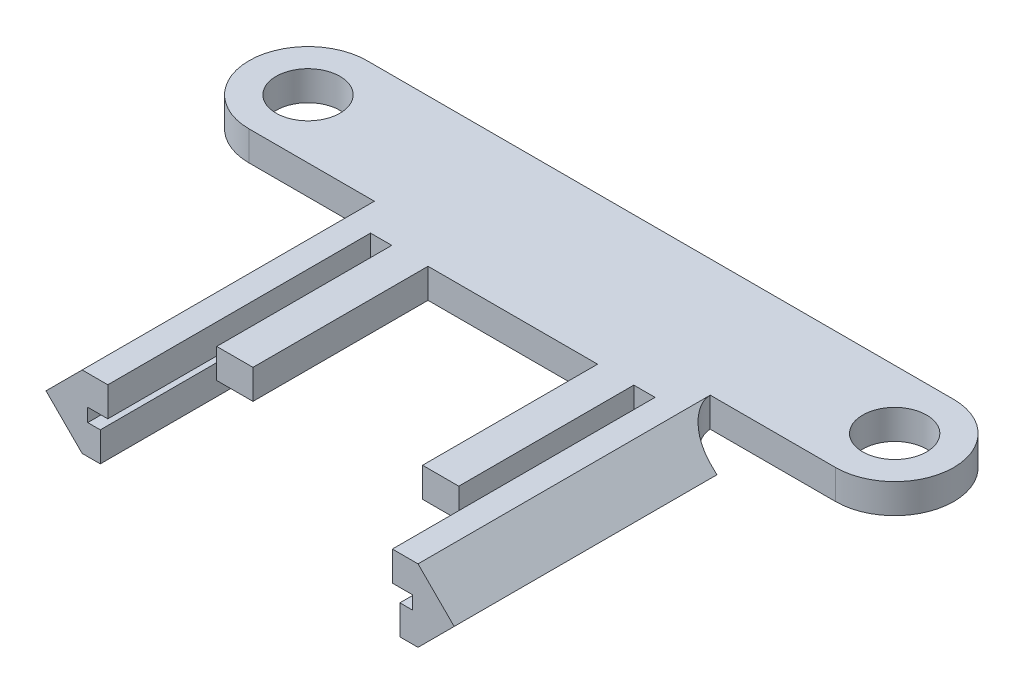
SolidWorks part; units mm, degrees
ref_plane "Front Plane" through (0, 0, 0) normal (0, 0, 1) x (1, 0, 0)
ref_plane "Top Plane" through (0, 0, 0) normal (0, 1, 0) x (1, 0, 0)
ref_plane "Right Plane" through (0, 0, 0) normal (1, 0, 0) x (0, 0, -1)
sketch "Sketch1" plane through (0, 0, 0) normal (0, 0, 1) x (1, 0, 0)
  line L0 (0.8255, 1.143) -> (0, 1.143)
  line L1 (0, 0) -> (0.8255, 0) construction
  line L2 (0, 0) -> (0, 1.143) construction
  line L3 (0, 1.143) -> (0.8255, 1.143) construction
  line L4 (0.8255, 0) -> (0.8255, 1.143) construction
  line L5 (0.4127, 1.143) -> (0.4128, 0) construction
  line L6 (0, 0.5715) -> (0.8255, 0.5715) construction
  line L7 (0.8255, 0) -> (0, 0)
  line L8 (0, 0) -> (-0.5715, 0.5715) construction
  line L9 (-0.5715, 0.5715) -> (0, 1.143) construction
  line L10 (25.9715, 0) -> (26.797, 0)
  line L11 (0.8255, 1.143) -> (25.9715, 1.143)
  line L12 (0.8255, 1.143) -> (0.8255, 0) construction
  line L13 (0.8255, 0) -> (25.9715, 0)
  line L14 (25.9715, 1.143) -> (25.9715, 0) construction
  line L15 (13.3985, 0) -> (13.3985, 1.143) construction
  line L16 (0.8255, 0.5715) -> (25.9715, 0.5715) construction
  line L17 (26.797, 0) -> (27.3685, 0.5715) construction
  line L18 (25.9715, 1.143) -> (26.797, 1.143)
  line L19 (27.3685, 0.5715) -> (26.797, 1.143) construction
  line L20 (-4.1636, 0.5715) -> (-1.0521, 3.683)
  line L21 (0.8255, 3.683) -> (-1.0521, 3.683)
  line L22 (0.8255, 3.683) -> (25.9715, 3.683)
  line L23 (25.9715, 3.683) -> (27.8491, 3.683)
  line L24 (30.9606, 0.5715) -> (27.8491, 3.683)
  line L25 (27.8491, -2.54) -> (30.9606, 0.5715)
  line L26 (25.9715, -2.54) -> (27.8491, -2.54)
  line L27 (0.8255, -2.54) -> (25.9715, -2.54)
  line L28 (0.8255, -2.54) -> (-1.0521, -2.54)
  line L29 (-1.0521, -2.54) -> (-4.1636, 0.5715)
  line L30 (0, 1.143) -> (-0.5715, 1.143)
  line L31 (-0.5715, 1.143) -> (-0.5715, 0)
  line L32 (-0.5715, 0) -> (0, 0)
  line L33 (26.797, 1.143) -> (27.3685, 1.143)
  line L34 (27.3685, 1.143) -> (27.3685, 0)
  line L35 (27.3685, 0) -> (26.797, 0)
  point P287 (13.3985, 0.5715)
  point P500 (0.4127, 0.5715)
  dimension "D1" = 1.143
  dimension "D2" = 0.8255
  dimension "D3" = 45
  dimension "D4" = 25.146
  dimension "D5" = 2.54
extrude "Boss-Extrude1" add sketch "Sketch1" along normal blind 22.606
sketch "Sketch2" plane through (0, 0, 22.606) normal (0, 0, 1) x (1, 0, 0)
  line L5 (13.3985, 0) -> (13.3985, -2.54) construction
  line L6 (-0.5715, 0) -> (27.3685, 0) construction
  line L7 (-1.0521, -2.54) -> (27.8491, -2.54) construction
  line L9 (0.508, 0) -> (26.289, 0)
  line L10 (0.508, 0) -> (0.508, -2.54)
  line L11 (0.508, -2.54) -> (26.289, -2.54)
  line L12 (26.289, 0) -> (26.289, -2.54)
  line L13 (13.3985, -2.54) -> (13.3985, 0) construction
  line L14 (0.508, -1.27) -> (26.289, -1.27) construction
  point P218 (13.3985, -1.27)
  dimension "D1" = 0.508
extrude "Cut-Extrude1" cut sketch "Sketch2" against normal blind 22.606
sketch "Sketch5" plane through (0, 0, 0) normal (0, 0, -1) x (-1, 0, 0)
  line L12 (-30.9606, 0.5715) -> (-27.3685, 0.5715)
  line L13 (-27.3685, 0.5715) -> (-27.3685, 1.143)
  line L14 (-27.3685, 1.143) -> (0.5715, 1.143)
  line L15 (0.5715, 1.143) -> (0.5715, 0.5715)
  line L16 (0.5715, 1.143) -> (0.5715, 0) construction
  line L17 (0.5715, 0.5715) -> (4.1636, 0.5715)
  line L18 (4.1636, 0.5715) -> (1.0521, 3.683)
  line L19 (1.0521, 3.683) -> (-27.8491, 3.683)
  line L20 (-27.8491, 3.683) -> (-30.9606, 0.5715)
extrude "Boss-Extrude2" add sketch "Sketch5" along normal blind 12.7
sketch "Sketch3" plane through (0, 3.683, 0) normal (0, 1, 0) x (1, 0, 0)
  line L0 (13.3985, 0) -> (13.3985, -22.606) construction
  line L1 (27.8491, 0) -> (-1.0521, 0) construction
  line L2 (27.8491, -22.606) -> (-1.0521, -22.606) construction
  line L3 (6.1023, -15.0622) -> (2.9845, -15.0622)
  line L4 (1.1557, 0) -> (25.6413, 0) construction
  line L5 (1.1557, 0) -> (1.1557, -22.606) construction
  line L6 (1.1557, -22.606) -> (25.6413, -22.606) construction
  line L7 (25.6413, 0) -> (25.6413, -22.606) construction
  line L8 (13.3985, -22.606) -> (13.3985, 0) construction
  line L9 (1.1557, -11.303) -> (25.6413, -11.303) construction
  line L10 (6.1023, 0) -> (20.6947, 0) construction
  line L11 (6.1023, 0) -> (6.1023, -15.0622)
  line L12 (6.1023, -15.0622) -> (20.6947, -15.0622) construction
  line L13 (20.6947, 0) -> (20.6947, -15.0622)
  line L14 (13.3985, -15.0622) -> (13.3985, 0) construction
  line L15 (6.1023, -7.5311) -> (20.6947, -7.5311) construction
  line L16 (2.9845, 0) -> (23.8125, 0) construction
  line L17 (2.9845, 0) -> (2.9845, -22.606) construction
  line L18 (2.9845, -22.606) -> (23.8125, -22.606) construction
  line L19 (23.8125, 0) -> (23.8125, -22.606) construction
  line L20 (13.3985, -22.606) -> (13.3985, 0) construction
  line L21 (2.9845, -11.303) -> (23.8125, -11.303) construction
  line L22 (2.9845, -15.0622) -> (2.9845, 0)
  line L23 (2.9845, 0) -> (1.1557, 0)
  line L24 (1.1557, 0) -> (1.1557, -22.606)
  line L25 (1.1557, -22.606) -> (25.6413, -22.606)
  line L26 (25.6413, -22.606) -> (25.6413, 0)
  line L27 (25.6413, 0) -> (23.8125, 0)
  line L28 (23.8125, 0) -> (23.8125, -15.0622)
  line L29 (23.8125, -15.0622) -> (20.6947, -15.0622)
  line L32 (6.1023, 0) -> (20.6947, 0)
  point P250 (13.3985, -11.303)
  point P383 (13.3985, -7.5311)
  point P386 (13.3985, -11.303)
  dimension "D1" = 24.4856
  dimension "D2" = 14.5923
  dimension "D3" = 15.0622
  dimension "D4" = 20.828
extrude "Cut-Extrude4" cut sketch "Sketch3" against normal up to vertex (2.54 mm away)
sketch "Sketch6" plane through (0, 0, -12.7) normal (0, 0, -1) x (-1, 0, 0)
  line L2 (-27.8491, 3.683) -> (-30.9606, 0.5715)
  line L3 (-30.9606, 0.5715) -> (-27.3685, 0.5715)
  line L4 (-27.3685, 0.5715) -> (-27.3685, 1.143)
  line L5 (-27.3685, 1.143) -> (-27.8491, 1.143)
  line L6 (-27.8491, 1.143) -> (-27.8491, 3.683)
  line L8 (-13.3985, 3.683) -> (-13.3985, 1.143) construction
  line L9 (-0.8255, 3.683) -> (-25.9715, 3.683) construction
  line L11 (1.0521, 1.143) -> (1.0521, 3.683)
  line L12 (0.5715, 1.143) -> (1.0521, 1.143)
  line L13 (0.5715, 0.5715) -> (0.5715, 1.143)
  line L14 (4.1636, 0.5715) -> (0.5715, 0.5715)
  line L15 (1.0521, 3.683) -> (4.1636, 0.5715)
extrude "Cut-Extrude5" cut sketch "Sketch6" against normal up to surface (12.7 mm away) up to face at (27.6875, -0.6562, 0)
fillet "Fillet1" radius 2.54 8 edges at (27.8491, 2.413, 0) (27.6088, 1.143, 0) (-0.8118, 1.143, 0) (-1.0521, 2.413, 0) (-0.0318, 0, 0) (27.3685, 0.5715, 0) (26.8288, 0, 0) (-0.5715, 0.5715, 0)
sketch "Sketch7" plane through (0, 1.143, 0) normal (0, -1, 0) x (1, 0, 0)
  line L2 (13.3985, 0) -> (13.3985, -12.7) construction
  line L3 (20.6947, 0) -> (6.1023, 0) construction
  line L4 (27.8491, -12.7) -> (-1.0521, -12.7) construction
  line L5 (-1.0521, -7.62) -> (27.8491, -7.62) construction
  line L6 (-1.0521, -2.54) -> (-1.0521, -12.7) construction
  line L7 (27.8491, -2.54) -> (27.8491, -12.7) construction
  line L8 (-1.0521, -7.62) -> (-11.8415, -7.62) construction
  line L9 (-1.0521, -2.54) -> (-11.8415, -2.54)
  line L10 (-1.0521, -2.54) -> (27.8491, -2.54)
  line L11 (27.8491, -2.54) -> (38.6385, -2.54)
  line L12 (27.8491, -12.7) -> (38.6385, -12.7)
  line L13 (-1.0521, -12.7) -> (27.8491, -12.7)
  line L14 (-1.0521, -12.7) -> (-11.8415, -12.7)
  line L15 (-11.8415, -2.54) -> (-11.8415, -12.7) construction
  circle A4 centre (-11.8415, -7.62) radius 2 construction
  circle A5 centre (38.6385, -7.62) radius 2 construction
  arc A6 (-11.8415, -12.7) -> (-11.8415, -2.54) centre (-11.8415, -7.62) cw
  arc A7 (38.6385, -12.7) -> (38.6385, -2.54) centre (38.6385, -7.62) ccw
  dimension "D1" = 50.48
  dimension "D2" = 4
extrude "Boss-Extrude3" add sketch "Sketch7" against normal up to surface (2.54 mm away) up to face at (13.3985, 3.683, 6.6774)
hole_wizard "M5 Clearance Hole1" positions "Sketch8" profile "Sketch9" hole size "M5" standard "ANSI Metric" end condition through all
sketch "Sketch8" plane through (0, 1.143, 0) normal (0, -1, 0) x (-1, 0, 0)
  point P6 (-38.6385, 7.62)
  point P10 (11.8415, 7.62)
sketch "Sketch9" plane through (38.6385, 1.143, -7.62) normal (1, 0, 0) x (0, 0, -1)
  line L0 (0, 0) -> (0, 2.54)
  line L1 (0, 2.54) -> (2.75, 2.54)
  line L2 (2.75, 2.54) -> (2.75, 0)
  line L5 (2.75, 0) -> (0, 0)
  line L11 (0, -6.35) -> (0, 107.95) construction
  dimension "Thru Hole Dia." = 5.5
  dimension "Thru Hole Depth" = 2.54
